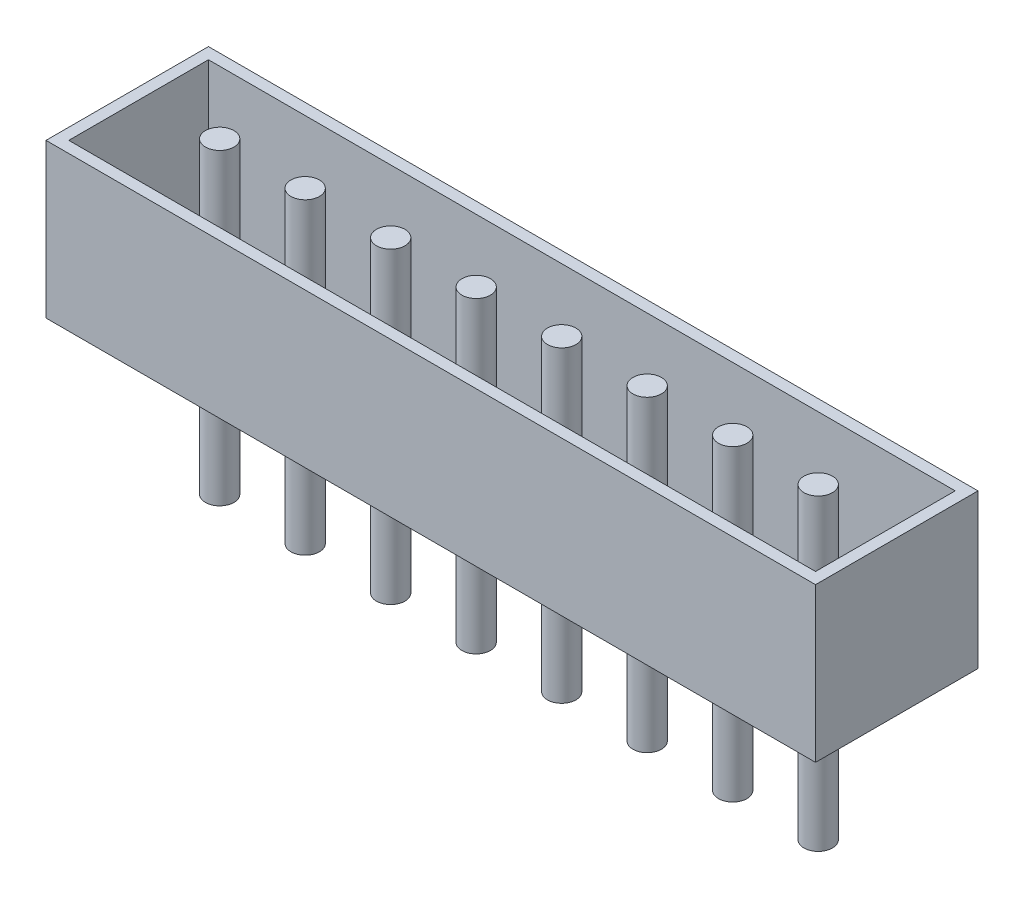
SolidWorks part; units mm, degrees
ref_plane "Front Plane" through (0, 0, 0) normal (0, 0, 1) x (1, 0, 0)
ref_plane "Top Plane" through (0, 0, 0) normal (0, 1, 0) x (1, 0, 0)
ref_plane "Right Plane" through (0, 0, 0) normal (1, 0, 0) x (0, 0, -1)
sketch "Sketch1" plane through (0, 0, 0) normal (0, 1, 0) x (1, 0, 0)
  line L1 (-4.9033, 1.3269) -> (8.5967, 1.3269)
  line L2 (-4.9033, 1.3269) -> (-4.9033, -1.5231)
  line L3 (-4.9033, -1.5231) -> (8.5967, -1.5231)
  line L4 (8.5967, 1.3269) -> (8.5967, -1.5231)
  line L5 (-4.9033, 1.3269) -> (-4.7033, 1.3269)
  line L6 (-4.9033, 1.3269) -> (-4.9033, -1.5231)
  line L7 (-4.9033, -1.5231) -> (-4.7033, -1.5231)
  line L8 (-4.7033, 1.3269) -> (-4.7033, -1.5231)
  line L9 (8.5967, 1.3269) -> (-4.9033, 1.3269)
  line L10 (8.5967, 1.3269) -> (8.5967, 1.1269)
  line L11 (8.5967, 1.1269) -> (-4.9033, 1.1269)
  line L12 (-4.9033, 1.3269) -> (-4.9033, 1.1269)
  line L13 (8.5967, -1.5231) -> (8.3967, -1.5231)
  line L14 (8.5967, -1.5231) -> (8.5967, 1.3269)
  line L15 (8.5967, 1.3269) -> (8.3967, 1.3269)
  line L16 (8.3967, -1.5231) -> (8.3967, 1.3269)
  line L17 (-4.9033, -1.5231) -> (8.5967, -1.5231)
  line L18 (-4.9033, -1.5231) -> (-4.9033, -1.3231)
  line L19 (-4.9033, -1.3231) -> (8.5967, -1.3231)
  line L20 (8.5967, -1.5231) -> (8.5967, -1.3231)
  circle A0 centre (-3.4033, 0.0237) radius 0.25
  circle A1 centre (-1.9033, 0.0237) radius 0.25
  circle A2 centre (-0.4033, 0.0237) radius 0.25
  circle A3 centre (1.0967, 0.0237) radius 0.25
  circle A4 centre (2.5967, 0.0237) radius 0.25
  circle A6 centre (4.0967, 0.0237) radius 0.25
  circle A7 centre (5.5967, 0.0237) radius 0.25
  circle A8 centre (7.0967, 0.0237) radius 0.25
  dimension "D3" = 0.2
  dimension "D1" = 13.5
  dimension "D2" = 2.85
  dimension "D4" = 0.2
  dimension "D5" = 0.2
  dimension "D6" = 0.2
  dimension "D7" = 2.85
  dimension "D8" = 13.5
  dimension "D9" = 2.85
  dimension "D10" = 13.5
extrude "Boss-Extrude1" add sketch "Sketch1" against normal blind 2.7 contours A4 | A3 | A2 | A1 | A0 | A8 | A7 | A6
extrude "Boss-Extrude3" add sketch "Sketch1<7>" along normal blind 2.7 separate body contours L6 L19 L8 L11 | L19 L8 L3 L16 | L16 L19 L4 L11 | L19 L2 L3 L8 | L19 L16 L3 L14 | L10 L11 L12 L9 region at (-4.8033, 0, 0.0981) region at (-4.8033, 0, 1.4231) region at (8.4967, 0, 0.0981) region at (1.8467, 0, 1.4231) region at (8.4967, 0, 1.4231)
sketch "Sketch1<7>" plane through (0, 0, 0) normal (0, 1, 0) x (1, 0, 0) same geometry as "Sketch1"
extrude "Boss-Extrude4" add sketch "Sketch1<8>" along normal blind 0.2 contours L8 L19 L16 L11 A8 A7 A6 A4 A3 A2 A1 A0 region at (1.8467, 0, 0.1044)
sketch "Sketch1<8>" plane through (0, 0, 0) normal (0, 1, 0) x (1, 0, 0) same geometry as "Sketch1"
extrude "Boss-Extrude5" add sketch "Sketch1<9>" along normal blind 2.7 contours A0 | A2 | A3 | A4 | A6 | A7 | A8 | A1 region at (-3.4033, 0, -0.0237) region at (-0.4033, 0, -0.0237) region at (1.0967, 0, -0.0237) region at (2.5967, 0, -0.0237) region at (4.0967, 0, -0.0237) region at (5.5967, 0, -0.0237) region at (7.0967, 0, -0.0237)
sketch "Sketch1<9>" plane through (0, 0, 0) normal (0, 1, 0) x (1, 0, 0) same geometry as "Sketch1"
